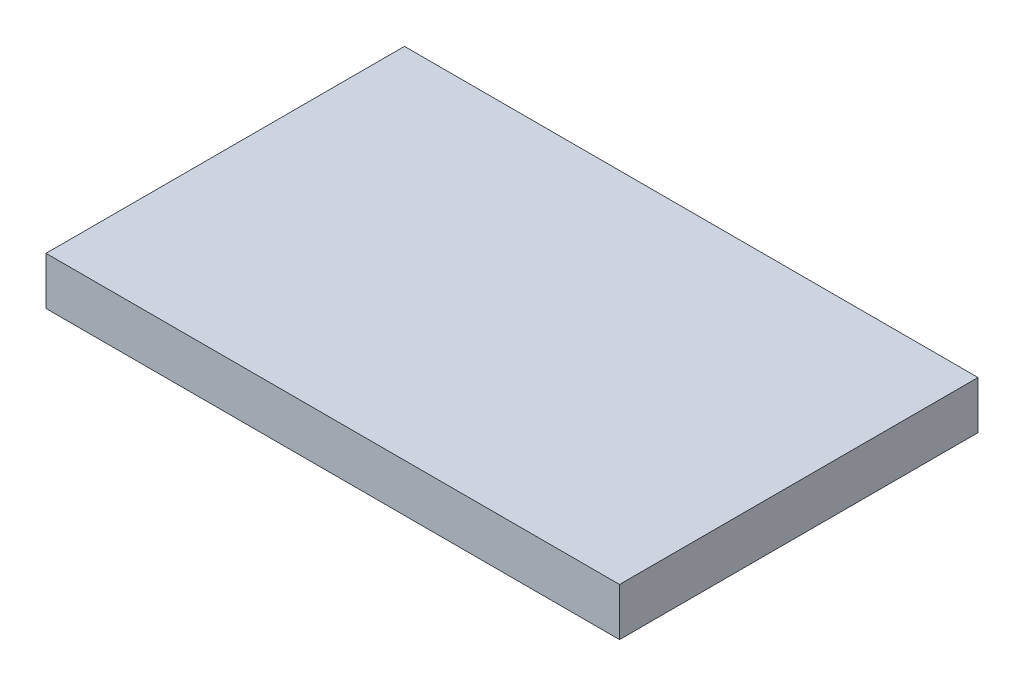
SolidWorks part; units mm, degrees
ref_plane "Front Plane" through (0, 0, 0) normal (0, 0, 1) x (1, 0, 0)
ref_plane "Top Plane" through (0, 0, 0) normal (0, 1, 0) x (1, 0, 0)
ref_plane "Right Plane" through (0, 0, 0) normal (1, 0, 0) x (0, 0, -1)
sketch "Sketch1" plane through (0, 0, 0) normal (0, 1, 0) x (1, 0, 0)
  line L1 (60, -37.5) -> (-60, -37.5)
  line L2 (60, -37.5) -> (60, 37.5)
  line L3 (60, 37.5) -> (-60, 37.5)
  line L4 (-60, -37.5) -> (-60, 37.5)
  line L5 (60, -37.5) -> (-60, 37.5) construction
  line L6 (60, 37.5) -> (-60, -37.5) construction
  point P0 (0, 0)
  point P5 (0, 0)
  dimension "D1" = 75
  dimension "D2" = 120
extrude "Boss-Extrude1" add sketch "Sketch1" along normal blind 10
